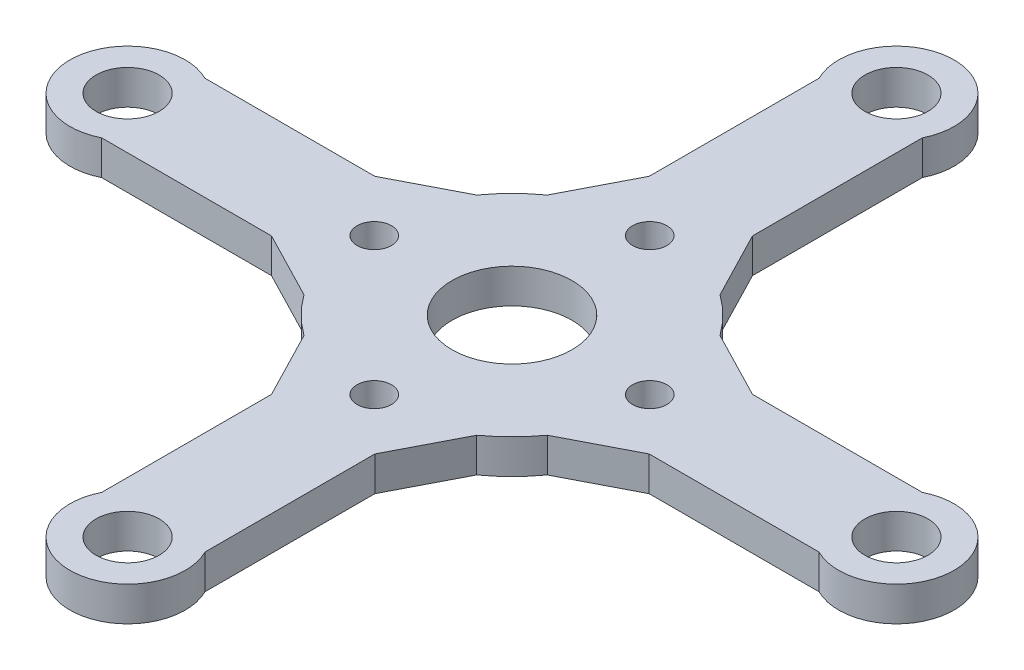
SolidWorks part; units mm, degrees
ref_plane "Alzado" through (0, 0, 0) normal (0, 0, 1) x (1, 0, 0)
ref_plane "Planta" through (0, 0, 0) normal (0, 1, 0) x (1, 0, 0)
ref_plane "Vista lateral" through (0, 0, 0) normal (1, 0, 0) x (0, 0, -1)
sketch "Sketch1" plane through (0, 0, 0) normal (0, 1, 0) x (1, 0, 0)
  line L0 (-4.5, 31.2517) -> (-4.5, 12.1963)
  line L1 (4.5, 31.2517) -> (4.5, 12.1963)
  line L2 (31.2517, 4.5) -> (12.1963, 4.5)
  line L3 (31.2517, -4.5) -> (12.1963, -4.5)
  line L4 (4.5, -31.2517) -> (4.5, -12.1963)
  line L5 (-4.5, -31.2517) -> (-4.5, -12.1963)
  line L6 (-31.2517, -4.5) -> (-12.1963, -4.5)
  line L7 (-31.2517, 4.5) -> (-12.1963, 4.5)
  arc A0 (-12.1963, -4.5) -> (-4.5, -12.1963) centre (0, 0) ccw
  arc A15 (-4.5, 12.1963) -> (-12.1963, 4.5) centre (0, 0) ccw
  arc A16 (12.1963, 4.5) -> (4.5, 12.1963) centre (0, 0) ccw
  arc A17 (4.5, -12.1963) -> (12.1963, -4.5) centre (0, 0) ccw
  circle A21 centre (0, -33.4949) radius 2.75
  circle A22 centre (-33.4949, 0) radius 2.75
  circle A23 centre (0, 33.4949) radius 2.75
  circle A24 centre (33.4949, 0) radius 2.75
  arc A25 (-31.2517, 4.5) -> (-31.2517, -4.5) centre (-33.4949, 0) ccw
  arc A27 (4.5, 31.2517) -> (-4.5, 31.2517) centre (0, 33.4949) ccw
  arc A28 (31.2517, -4.5) -> (31.2517, 4.5) centre (33.4949, 0) ccw
  arc A29 (-4.5, -31.2517) -> (4.5, -31.2517) centre (0, -33.4949) ccw
  point P29 (0, 0)
  point P34 (0, 0)
  point P35 (0, 0)
  point P47 (0, 0)
  dimension "D1" = 26
  dimension "D2" = 4
  dimension "D3" = 4
  dimension "D4" = 4
  dimension "5" = 5.5
extrude "Boss-Extrude1" add sketch "Sketch1" along normal blind 3
chamfer "Chamfer1" distance 5 8 edges at (-12.1963, 1.5, -4.5) (-4.5, 1.5, -12.1963) (4.5, 1.5, -12.1963) (12.1963, 1.5, -4.5) (12.1963, 1.5, 4.5) (4.5, 1.5, 12.1963) (-4.5, 1.5, 12.1963) (-12.1963, 1.5, 4.5)
sketch "Sketch2" plane through (0, 3, 0) normal (0, 1, 0) x (1, 0, 0)
  circle A0 centre (0, 0) radius 6.8806 construction
sketch "Sketch3" plane through (0, 3, 0) normal (0, 1, 0) x (1, 0, 0)
  line L0 (-4.5, -16.4534) -> (4.5, -16.4534) construction
sketch "Sketch5" plane through (0, 3, 0) normal (0, 1, 0) x (1, 0, 0)
  circle A1 centre (0, 0) radius 5.2263
  circle A2 centre (0, 12) radius 1.5
  circle A3 centre (12, 0) radius 1.5
  circle A4 centre (0, -12) radius 1.5
  circle A5 centre (-12, 0) radius 1.5
  point P15 (0, 0)
  dimension "D1" = 10.4526
  dimension "D2" = 4
extrude "Cut-Extrude2" cut sketch "Sketch5" against normal blind 7.2
